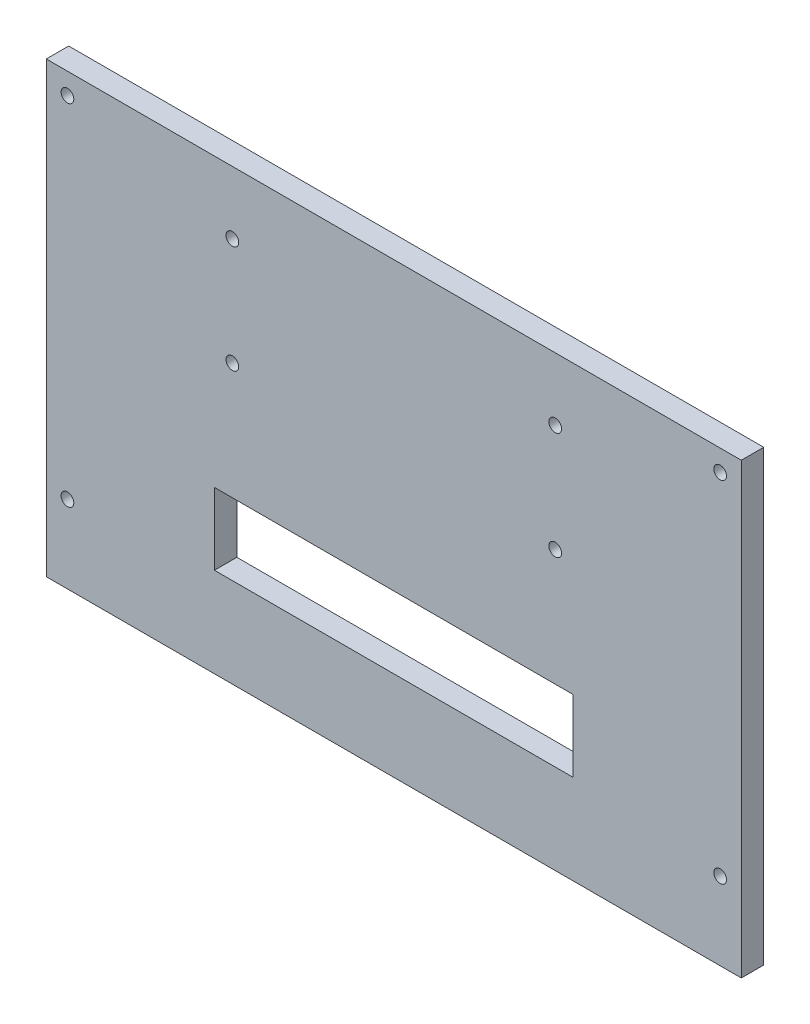
SolidWorks part; units mm, degrees
material "Acrylic (Medium-high impact)"
ref_plane "Front Plane" through (0, 0, 0) normal (0, 0, 1) x (1, 0, 0)
ref_plane "Top Plane" through (0, 0, 0) normal (0, 1, 0) x (1, 0, 0)
ref_plane "Right Plane" through (0, 0, 0) normal (1, 0, 0) x (0, 0, -1)
sketch "Sketch1" plane through (0, 0, 0) normal (0, 0, 1) x (1, 0, 0)
  line L1 (196.85, 127) -> (0, 127)
  line L2 (196.85, 127) -> (196.85, 0)
  line L3 (196.85, 0) -> (0, 0)
  line L4 (0, 127) -> (0, 0)
  line L5 (196.85, 127) -> (0, 0) construction
  line L6 (196.85, 0) -> (0, 127) construction
  point P0 (98.425, 63.5)
  dimension "D1" = 127
  dimension "D2" = 196.85
extrude "Boss-Extrude1" add sketch "Sketch1" along normal blind 6.35
hole_wizard "M3 Clearance Hole1" positions "Sketch2" profile "Sketch3" hole size "M3" standard "ANSI Metric" end condition through all
sketch "Sketch2" plane through (0, 0, 6.35) normal (0, 0, 1) x (1, 0, 0)
  line L0 (0, 127) -> (0, 0) construction
  line L1 (196.85, 127) -> (0, 127) construction
  line L2 (196.85, 0) -> (196.85, 127) construction
  line L3 (0, 0) -> (196.85, 0) construction
  point P0 (5.9944, 121.0056)
  point P2 (5.9944, 21.9964)
  point P4 (190.8556, 21.9964)
  point P6 (190.8556, 121.0056)
  dimension "D1" = 5.9944
  dimension "D2" = 5.9944
  dimension "D3" = 5.9944
  dimension "D4" = 21.9964
sketch "Sketch3" plane through (5.9944, 121.0056, 6.35) normal (1, 0, 0) x (0, -1, 0)
  line L0 (0, 0) -> (0, 6.35)
  line L1 (0, 6.35) -> (1.8, 6.35)
  line L2 (1.8, 6.35) -> (1.8, 0)
  line L5 (1.8, 0) -> (0, 0)
  line L11 (0, -6.35) -> (0, 107.95) construction
  dimension "Thru Hole Dia." = 3.6
  dimension "Thru Hole Depth" = 6.35
sketch "Sketch4" plane through (0, 0, 6.35) normal (0, 0, 1) x (1, 0, 0)
  line L0 (0, 127) -> (0, 0) construction
  line L1 (46.99, 107.95) -> (50.4952, 107.95)
  line L2 (46.99, 107.95) -> (46.99, 44.45)
  line L3 (46.99, 44.45) -> (50.4952, 44.45)
  line L4 (50.4952, 107.95) -> (50.4952, 44.45)
  line L5 (146.3548, 107.95) -> (149.86, 107.95)
  line L6 (146.3548, 107.95) -> (146.3548, 44.45)
  line L7 (146.3548, 44.45) -> (149.86, 44.45)
  line L8 (149.86, 107.95) -> (149.86, 44.45)
  line L9 (196.85, 0) -> (196.85, 127) construction
  line L10 (196.85, 127) -> (0, 127) construction
  dimension "D1" = 3.5052
  dimension "D2" = 63.5
  dimension "D3" = 46.99
  dimension "D4" = 46.99
  dimension "D5" = 19.05
extrude "Cut-Extrude1" [suppressed] cut sketch "Sketch4" against normal through all
sketch "Sketch5" plane through (0, 0, 6.35) normal (0, 0, 1) x (1, 0, 0)
  line L0 (0, 36.1092) -> (76.2, 25.4)
  line L1 (0, 127) -> (0, 0) construction
  line L2 (76.2, 25.4) -> (120.65, 25.4)
  line L3 (120.65, 25.4) -> (196.85, 36.1092)
  line L4 (196.85, 0) -> (196.85, 127) construction
  line L5 (196.85, 36.1092) -> (196.85, 0)
  line L6 (196.85, 0) -> (0, 0)
  line L7 (0, 0) -> (0, 36.1092)
  dimension "D1" = 8
  dimension "D2" = 8
  dimension "D3" = 76.2
  dimension "D4" = 76.2
  dimension "D5" = 25.4
extrude "Cut-Extrude2" [suppressed] cut sketch "Sketch5" against normal through all
sketch "Sketch7" plane through (0, 0, 6.35) normal (0, 0, 1) x (1, 0, 0)
  line L0 (0, 0) -> (196.85, 0) construction
  line L1 (47.625, 45.72) -> (149.225, 45.72)
  line L2 (47.625, 45.72) -> (47.625, 25.4)
  line L3 (47.625, 25.4) -> (149.225, 25.4)
  line L4 (149.225, 45.72) -> (149.225, 25.4)
  line L5 (47.625, 45.72) -> (149.225, 25.4) construction
  line L6 (47.625, 25.4) -> (149.225, 45.72) construction
  point P0 (98.425, 35.56)
  point P5 (98.425, 0)
  dimension "D1" = 20.32
  dimension "D2" = 101.6
  dimension "D3" = 25.4
extrude "tubingslot" cut sketch "Sketch7" against normal through all
hole_wizard "M3 Clearance Hole2" positions "Sketch8" profile "Sketch9" hole size "M3" standard "ANSI Metric" end condition through all
sketch "Sketch8" plane through (0, 0, 6.35) normal (0, 0, 1) x (1, 0, 0)
  line L0 (52.705, 109.22) -> (144.145, 109.22) construction
  line L2 (98.425, 109.22) -> (98.425, 127) construction
  line L3 (196.85, 127) -> (0, 127) construction
  point P0 (52.705, 109.22)
  point P2 (144.145, 109.22)
  point P4 (52.705, 78.74)
  point P6 (144.145, 78.74)
  dimension "D1" = 91.44
  dimension "D2" = 30.48
  dimension "D3" = 17.78
sketch "Sketch9" plane through (52.705, 109.22, 6.35) normal (1, 0, 0) x (0, -1, 0)
  line L0 (0, 0) -> (0, 6.35)
  line L1 (0, 6.35) -> (1.8, 6.35)
  line L2 (1.8, 6.35) -> (1.8, 0)
  line L5 (1.8, 0) -> (0, 0)
  line L11 (0, -6.35) -> (0, 107.95) construction
  dimension "Thru Hole Dia." = 3.6
  dimension "Thru Hole Depth" = 6.35
